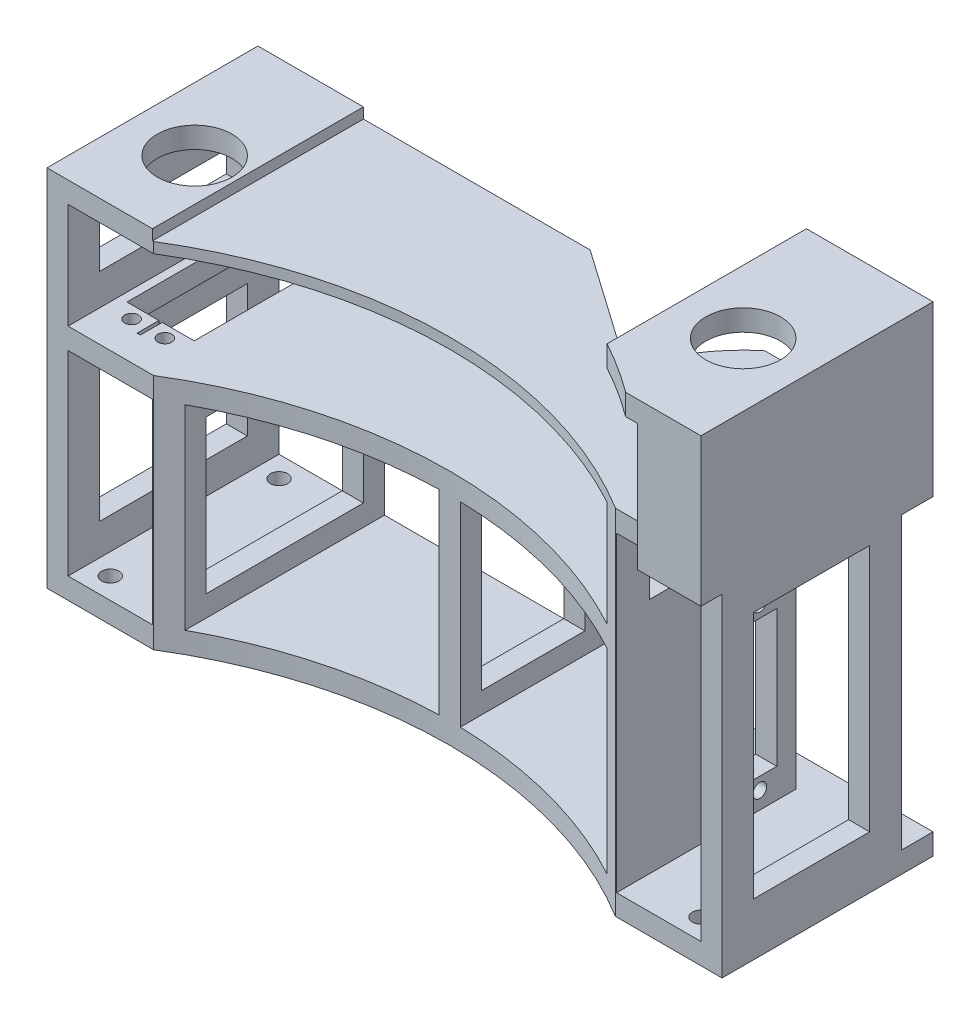
SolidWorks part; units mm, degrees
ref_plane "Front Plane" through (0, 0, 0) normal (0, 0, 1) x (1, 0, 0)
ref_plane "Top Plane" through (0, 0, 0) normal (0, 1, 0) x (1, 0, 0)
ref_plane "Right Plane" through (0, 0, 0) normal (1, 0, 0) x (0, 0, -1)
sketch "Sketch1" plane through (0, 0, 0) normal (0, 0, 1) x (1, 0, 0)
  line L0 (-101.6, 106.425) -> (101.6, 106.425)
  line L1 (-101.6, 0) -> (101.6, 0)
  line L2 (-101.6, 0) -> (-101.6, 106.425)
  line L4 (101.6, 0) -> (101.6, 106.425)
  point P5 (0, 0)
  dimension "D1" = 203.2
  dimension "D2" = 106.425
extrude "Boss-Extrude1" add sketch "Sketch1" along normal mid plane 63.5 contours L1 L4 L0 L2 | L0 region at (0, 53.2125, 0)
sketch "Sketch4" plane through (0, 0, -31.75) normal (0, 0, -1) x (-1, 0, 0)
  line L0 (-101.6, 0) -> (-101.6, 106.425) construction
  line L1 (101.6, 0) -> (101.6, 106.425) construction
  line L2 (-95.25, 103.25) -> (95.25, 103.25)
  line L3 (-95.25, 103.25) -> (-95.25, 71.5)
  line L4 (-95.25, 71.5) -> (95.25, 71.5)
  line L5 (95.25, 103.25) -> (95.25, 71.5)
  line L11 (-95.25, 65.15) -> (95.25, 65.15)
  line L12 (-95.25, 65.15) -> (-95.25, 6.35)
  line L13 (-95.25, 6.35) -> (95.25, 6.35)
  line L14 (95.25, 65.15) -> (95.25, 6.35)
  line L15 (101.6, 0) -> (-101.6, 0) construction
  dimension "D4" = 6.35
  dimension "D1" = 6.35
  dimension "D2" = 71.5
  dimension "D3" = 6.35
  dimension "D5" = 6.35
  dimension "D6" = 31.75
extrude "Cut-Extrude2" cut sketch "Sketch4" against normal through all
sketch "Sketch8" plane through (0, 0, 0) normal (0, 0, 1) x (1, 0, 0)
  line L0 (-95.25, 65.15) -> (95.25, 65.15) construction
  line L1 (-69.85, 65.15) -> (-63.5, 65.15)
  line L2 (-69.85, 65.15) -> (-69.85, 6.35)
  line L3 (-69.85, 6.35) -> (-63.5, 6.35)
  line L4 (-63.5, 65.15) -> (-63.5, 6.35)
  line L5 (95.25, 6.35) -> (-95.25, 6.35) construction
  line L6 (-95.25, 103.25) -> (95.25, 103.25) construction
  line L7 (63.5, 103.25) -> (69.85, 103.25)
  line L8 (63.5, 103.25) -> (63.5, 6.35)
  line L9 (63.5, 6.35) -> (69.85, 6.35)
  line L10 (69.85, 103.25) -> (69.85, 6.35)
  line L11 (95.25, 65.15) -> (95.25, 6.35) construction
  line L12 (-95.25, 6.35) -> (-95.25, 65.15) construction
  line L13 (-101.6, 0) -> (101.6, 0) construction
  line L14 (-3.175, 65.15) -> (3.175, 65.15)
  line L15 (-3.175, 65.15) -> (-3.175, 6.35)
  line L16 (-3.175, 6.35) -> (3.175, 6.35)
  line L17 (3.175, 65.15) -> (3.175, 6.35)
  point P24 (0, 0)
  point P25 (0, 6.35)
  dimension "D1" = 6.35
  dimension "D2" = 6.35
  dimension "D3" = 25.4
  dimension "D4" = 25.4
  dimension "D5" = 6.35
extrude "Boss-Extrude2" add sketch "Sketch8" along normal up to surface (31.75 mm away) from surface up to face at (0, 87.375, 31.75) starting at face at (0, 87.375, -31.75)
sketch "Sketch15" plane through (0, 103.25, 0) normal (0, -1, 0) x (1, 0, 0)
  line L4 (69.85, 31.75) -> (69.85, -31.75)
  line L5 (69.85, -31.75) -> (95.25, -31.75)
  line L6 (95.25, -31.75) -> (95.25, 31.75)
  line L7 (95.25, 31.75) -> (69.85, 31.75)
  line L8 (69.85, 31.75) -> (69.85, -31.75)
  line L9 (69.85, -31.75) -> (95.25, -31.75)
  line L10 (95.25, -31.75) -> (95.25, 31.75)
  line L11 (95.25, 31.75) -> (69.85, 31.75)
  dimension "D1" = 0
extrude "Boss-Extrude4" add sketch "Sketch15" along normal blind 3.175
sketch "Sketch2" plane through (0, 71.5, 0) normal (0, 1, 0) x (1, 0, 0)
  line L0 (-92.677, 24.55) -> (-72.423, -16.604) construction
  line L29 (-92.677, 24.55) -> (-83.05, 24.55)
  line L30 (-92.677, 24.55) -> (-92.677, -16.604)
  line L31 (-92.677, -16.604) -> (-83.05, -16.604)
  line L34 (-72.423, 24.55) -> (-72.423, -16.604)
  line L58 (69.85, 31.75) -> (69.85, -31.75)
  line L59 (69.85, -31.75) -> (95.25, -31.75)
  line L60 (95.25, -31.75) -> (95.25, 31.75)
  line L61 (95.25, 31.75) -> (69.85, 31.75)
  line L62 (69.85, 31.75) -> (69.85, -31.75)
  line L63 (69.85, -31.75) -> (95.25, -31.75)
  line L64 (95.25, -31.75) -> (95.25, 31.75)
  line L65 (95.25, 31.75) -> (69.85, 31.75)
  line L78 (-72.423, 24.55) -> (-92.677, -16.604) construction
  line L79 (-87.55, 28.273) -> (-77.55, -20.327) construction
  line L80 (-87.55, -20.327) -> (-77.55, 28.273) construction
  line L81 (-82.05, -16.604) -> (-72.423, -16.604)
  line L82 (-82.05, -16.604) -> (-82.05, -23.208)
  line L83 (-82.05, -23.208) -> (-83.05, -23.208)
  line L84 (-83.05, -16.604) -> (-83.05, -23.208)
  line L85 (-82.55, 3.973) -> (-13.3966, 3.973) construction
  line L86 (-82.05, 31.154) -> (-83.05, 31.154)
  line L87 (-82.05, 24.55) -> (-82.05, 31.154)
  line L88 (-83.05, 24.55) -> (-83.05, 31.154)
  line L89 (-82.05, 24.55) -> (-72.423, 24.55)
  line L90 (-101.6, -31.75) -> (101.6, -31.75) construction
  line L91 (-101.6, -31.75) -> (-101.6, 31.75) construction
  circle A12 centre (-87.55, -20.327) radius 2.1
  circle A13 centre (-77.55, -20.327) radius 2.1
  circle A14 centre (-87.55, 28.273) radius 2.1
  circle A15 centre (-77.55, 28.273) radius 2.1
  point P8 (-82.55, -23.208)
  point P17 (-82.55, 3.973)
  point P18 (-82.55, 3.973)
  point P27 (-82.55, -6.35)
  dimension "D3" = 48.6
  dimension "D4" = 4.2
  dimension "D2" = 10
  dimension "D5" = 41.154
  dimension "D6" = 20.254
  dimension "D7" = 1
  dimension "D8" = 6.604
  dimension "D9" = 30.9
  dimension "D10" = 25.4
  dimension "D11" = 0
  dimension "D12" = 19.05
extrude "Cut-Extrude3" cut sketch "Sketch2" against normal up to next
sketch "Sketch9" plane through (0, 106.425, 0) normal (0, 1, 0) x (1, 0, 0)
  line L0 (72.423, 24.55) -> (92.677, -16.604) construction
  line L1 (72.423, 24.55) -> (82.05, 24.55)
  line L2 (72.423, 24.55) -> (72.423, -16.604)
  line L3 (72.423, -16.604) -> (82.05, -16.604)
  line L4 (92.677, 24.55) -> (92.677, -16.604)
  line L5 (92.677, 24.55) -> (72.423, -16.604) construction
  line L6 (77.55, 28.273) -> (87.55, -20.327) construction
  line L7 (77.55, -20.327) -> (87.55, 28.273) construction
  line L8 (83.05, -16.604) -> (92.677, -16.604)
  line L9 (83.05, -16.604) -> (83.05, -23.208)
  line L10 (83.05, -23.208) -> (82.05, -23.208)
  line L11 (82.05, -16.604) -> (82.05, -23.208)
  line L12 (82.55, 3.973) -> (164.4034, 3.973) construction
  line L13 (83.05, 31.154) -> (82.05, 31.154)
  line L14 (83.05, 24.55) -> (83.05, 31.154)
  line L15 (82.05, 24.55) -> (82.05, 31.154)
  line L16 (83.05, 24.55) -> (92.677, 24.55)
  line L17 (101.6, -31.75) -> (101.6, 31.75) construction
  line L19 (-101.6, -31.75) -> (101.6, -31.75) construction
  circle A0 centre (77.55, -20.327) radius 2.1
  circle A1 centre (87.55, -20.327) radius 2.1
  circle A2 centre (77.55, 28.273) radius 2.1
  circle A3 centre (87.55, 28.273) radius 2.1
  point P8 (82.55, -23.208)
  point P17 (82.55, 3.973)
  point P18 (82.55, 3.973)
  point P27 (82.55, -6.35)
  dimension "D3" = 4.2
  dimension "D1" = 10
  dimension "D2" = 48.6
  dimension "D4" = 41.154
  dimension "D5" = 20.254
  dimension "D6" = 1
  dimension "D7" = 6.604
  dimension "D8" = 30.9
  dimension "D9" = 19.05
  dimension "D10" = 25.4
extrude "Cut-Extrude4" cut sketch "Sketch9" against normal up to next
sketch "Sketch12" plane through (0, 0, 0) normal (0, 1, 0) x (1, 0, 0)
  line L0 (-63.5, -31.75) -> (-63.5, 31.75) construction
  line L1 (-69.85, -31.75) -> (-95.25, -31.75) construction
  line L2 (-95.25, -31.75) -> (-95.25, 31.75) construction
  line L3 (-101.6, 31.75) -> (101.6, 31.75) construction
  circle A0 centre (-88.9, 25.4) radius 2.6
  circle A1 centre (-88.9, -25.4) radius 2.6
  circle A2 centre (-31.75, 25.4) radius 2.6
  dimension "D1" = 5.2
  dimension "D2" = 6.35
  dimension "D3" = 6.35
  dimension "D4" = 6.35
  dimension "D5" = 31.75
extrude "Cut-Extrude7" cut sketch "Sketch12" along normal up to surface (6.35 mm away) and the other way through all up to face at (-33.3375, 6.35, 0)
mirror "Mirror1" about plane through (0, 0, 0) normal (1, 0, 0) of "Cut-Extrude7"
sketch "Sketch16" plane through (0, 106.425, 0) normal (0, 1, 0) x (1, 0, 0)
  line L2 (-69.85, 31.75) -> (-101.6, 31.75)
  line L3 (-101.6, 31.75) -> (-101.6, -31.75)
  line L12 (-101.6, -31.75) -> (-69.85, -31.75)
  line L13 (-69.85, 31.75) -> (-69.85, -31.75)
  dimension "D1" = 31.75
extrude "Boss-Extrude5" add sketch "Sketch16" along normal blind 3.175
sketch "Sketch17" plane through (0, 109.6, 0) normal (0, 1, 0) x (1, 0, 0)
  line L0 (-101.6, -31.75) -> (-69.85, -31.75) construction
  line L1 (-101.6, 31.75) -> (-101.6, -31.75) construction
  circle A0 centre (-82.55, -6.35) radius 11.2395
  dimension "D3" = 22.479
  dimension "D1" = 25.4
  dimension "D2" = 19.05
extrude "Cut-Extrude8" cut sketch "Sketch17" against normal up to next
sketch "Sketch18" plane through (0, 106.425, 0) normal (0, 1, 0) x (1, 0, 0)
  line L5 (101.6, -31.75) -> (101.6, 31.75) construction
  line L6 (-69.85, -31.75) -> (101.6, -31.75) construction
  line L14 (101.6, -31.75) -> (101.6, 31.75)
  line L15 (101.6, 31.75) -> (95.25, 31.75)
  line L16 (95.25, -31.75) -> (95.25, 31.75)
  line L22 (95.25, -31.75) -> (82.55, -31.75)
  line L23 (101.6, -31.75) -> (101.6, -38.1)
  line L24 (101.6, -38.1) -> (82.55, -38.1)
  line L25 (82.55, -31.75) -> (82.55, -38.1)
  dimension "D4" = 6.35
  dimension "D5" = 19.05
extrude "Boss-Extrude6" add sketch "Sketch18" along normal blind 38.1 from surface starting at face at (87.55, 100.075, 18.227)
sketch "Sketch20" plane through (0, 138.175, 0) normal (0, 1, 0) x (1, 0, 0)
  line L1 (63.5, 31.75) -> (101.6, 31.75)
  line L2 (63.5, 31.75) -> (63.5, -38.1)
  line L3 (63.5, -38.1) -> (101.6, -38.1)
  line L4 (101.6, 31.75) -> (101.6, -38.1)
  line L6 (-69.85, -31.75) -> (82.55, -31.75) construction
  circle A0 centre (82.55, -6.35) radius 11.2395
  dimension "D2" = 19.05
  dimension "D1" = 22.479
  dimension "D4" = 38.1
  dimension "D3" = 25.4
extrude "Boss-Extrude7" add sketch "Sketch20" along normal blind 6.35
sketch "Sketch10" plane through (0, 106.425, 0) normal (0, 1, 0) x (1, 0, 0)
  circle A3 centre (0, -144.78) radius 131.1117 construction
  circle A4 centre (0, -144.78) radius 131.1117 construction
  circle A5 centre (0, -144.78) radius 132.6992
  dimension "D1" = 1.5875
extrude "Cut-Extrude5" cut sketch "Sketch10" against normal through all both and the other way through all
sketch "Sketch21" plane through (0, 106.425, 0) normal (0, 1, 0) x (1, 0, 0)
  line L5 (34.6759, 6.35) -> (-1.5991, 31.75)
  line L6 (-69.85, 31.75) -> (95.25, 31.75) construction
  line L7 (-1.5991, 31.75) -> (50.9018, 31.75)
  arc A1 (34.6759, 6.35) -> (50.9018, 31.75) centre (82.55, -6.35) cw
  dimension "D2" = 49.53
  dimension "D1" = 35
  dimension "D3" = 25.4
extrude "Cut-Extrude10" cut sketch "Sketch21" against normal up to surface (3.175 mm away) up to face at (-82.55, 103.25, 17.5895)
sketch "Sketch32" plane through (0, 6.35, 0) normal (0, 1, 0) x (1, 0, 0)
  line L4 (-88.9, -25.4) -> (-76.2, -25.4)
  line L5 (-88.9, -25.4) -> (-76.2, -25.4)
  line L6 (76.2, -25.4) -> (88.9, -25.4)
  line L7 (76.2, -25.4) -> (88.9, -25.4)
  line L8 (76.2, 25.4) -> (76.2, -25.4)
  line L9 (88.9, -25.4) -> (88.9, 25.4)
  line L10 (88.9, 25.4) -> (76.2, 25.4)
  line L11 (76.2, 25.4) -> (76.2, -25.4)
  line L12 (88.9, -16.45) -> (88.9, 16.45)
  line L13 (79.95, 25.4) -> (76.2, 25.4)
  line L32 (-57.15, 25.4) -> (-57.15, -18.0181)
  line L33 (-9.525, -6.0574) -> (-9.525, 25.4)
  line L40 (-76.2, -25.4) -> (-76.2, 25.4)
  line L41 (-76.2, 25.4) -> (-88.9, 25.4)
  line L42 (-88.9, 25.4) -> (-88.9, -25.4)
  line L43 (-76.2, -25.4) -> (-76.2, 25.4)
  line L44 (-76.2, 25.4) -> (-79.95, 25.4)
  line L45 (-88.9, 16.45) -> (-88.9, -16.45)
  line L48 (-9.525, 25.4) -> (-57.15, 25.4)
  line L49 (-57.15, 25.4) -> (-57.15, -18.0181)
  line L50 (-9.525, -6.0574) -> (-9.525, 25.4)
  line L67 (-9.525, 25.4) -> (-22.8, 25.4)
  line L68 (-40.7, 25.4) -> (-57.15, 25.4)
  line L69 (22.8, 25.4) -> (9.525, 25.4)
  line L71 (9.525, 25.4) -> (9.525, -6.0574)
  line L72 (57.15, -18.0181) -> (57.15, 25.4)
  line L73 (57.15, 25.4) -> (9.525, 25.4)
  line L74 (9.525, 25.4) -> (9.525, -6.0574)
  line L75 (57.15, -18.0181) -> (57.15, 25.4)
  line L76 (57.15, 25.4) -> (40.7, 25.4)
  circle A2 centre (88.9, 25.4) radius 8.95
  arc A3 (79.95, 25.4) -> (88.9, 16.45) centre (88.9, 25.4) ccw
  circle A9 centre (88.9, -25.4) radius 8.95
  arc A10 (88.9, -16.45) -> (81.9575, -19.7516) centre (88.9, -25.4) ccw
  circle A13 centre (-31.75, 25.4) radius 8.95
  arc A26 (-40.7, 25.4) -> (-22.8, 25.4) centre (-31.75, 25.4) ccw
  circle A27 centre (-88.9, 25.4) radius 8.95
  arc A28 (-88.9, 16.45) -> (-79.95, 25.4) centre (-88.9, 25.4) ccw
  circle A30 centre (-88.9, -25.4) radius 8.95
  arc A31 (-80.2186, -23.2237) -> (-88.9, -16.45) centre (-88.9, -25.4) ccw
  circle A33 centre (31.75, 25.4) radius 8.95
  arc A35 (22.8, 25.4) -> (40.7, 25.4) centre (31.75, 25.4) ccw
  arc A38 (-9.525, -6.0574) -> (-57.15, -18.0181) centre (0, -144.78) ccw
  arc A39 (-9.525, -6.0574) -> (-57.15, -18.0181) centre (0, -144.78) ccw
  arc A42 (57.15, -18.0181) -> (9.525, -6.0574) centre (0, -144.78) ccw
  arc A43 (57.15, -18.0181) -> (9.525, -6.0574) centre (0, -144.78) ccw
  dimension "D1" = 6.35
  dimension "D2" = 6.35
  dimension "D3" = 6.35
  dimension "D4" = 6.35
  dimension "D5" = 6.35
  dimension "D6" = 6.35
  dimension "D7" = 6.35
  dimension "D8" = 6.35
  dimension "D9" = 6.35
  dimension "D10" = 6.35
extrude "Cut-Extrude19" cut sketch "Sketch32" against normal up to next rebuild error yes
sketch "Sketch23" plane through (0, 0, -31.75) normal (0, 0, -1) x (-1, 0, 0)
  line L1 (-101.6, 6.35) -> (-57.15, 6.35)
  line L2 (-101.6, 6.35) -> (-101.6, 93.725)
  line L3 (-101.6, 93.725) -> (-57.15, 93.725)
  line L4 (-57.15, 6.35) -> (-57.15, 93.725)
  line L7 (-63.5, 71.5) -> (95.25, 71.5) construction
  line L9 (-63.5, 65.15) -> (-63.5, 6.35) construction
  line L10 (-101.6, 0) -> (-101.6, 144.525) construction
  line L11 (-63.5, 6.35) -> (-3.175, 6.35) construction
  dimension "D1" = 6.35
  dimension "D2" = 22.225
extrude "Cut-Extrude11" cut sketch "Sketch23" against normal blind 9.525
sketch "Sketch24" plane through (63.5, 0, 0) normal (-1, 0, 0) x (0, 0, 1)
  line L0 (-16.477, 56.354) -> (3.777, 15.2) construction
  line L1 (-16.477, 56.354) -> (-6.85, 56.354)
  line L2 (-16.477, 56.354) -> (-16.477, 15.2)
  line L3 (-16.477, 15.2) -> (-6.85, 15.2)
  line L4 (3.777, 56.354) -> (3.777, 15.2)
  line L5 (3.777, 56.354) -> (-16.477, 15.2) construction
  line L6 (-11.35, 60.077) -> (-1.35, 11.477) construction
  line L7 (-11.35, 11.477) -> (-1.35, 60.077) construction
  line L8 (-5.85, 15.2) -> (3.777, 15.2)
  line L9 (-5.85, 15.2) -> (-5.85, 8.596)
  line L10 (-5.85, 8.596) -> (-6.85, 8.596)
  line L11 (-6.85, 15.2) -> (-6.85, 8.596)
  line L12 (-6.35, 35.777) -> (65.4757, 35.777) construction
  line L13 (-5.85, 62.958) -> (-6.85, 62.958)
  line L14 (-5.85, 56.354) -> (-5.85, 62.958)
  line L15 (-6.85, 56.354) -> (-6.85, 62.958)
  line L16 (-5.85, 56.354) -> (3.777, 56.354)
  line L17 (-22.225, 65.15) -> (-22.225, 6.35) construction
  line L18 (28.2603, 65.15) -> (-22.225, 65.15) construction
  circle A0 centre (-11.35, 11.477) radius 2.1
  circle A1 centre (-1.35, 11.477) radius 2.1
  circle A2 centre (-11.35, 60.077) radius 2.1
  circle A3 centre (-1.35, 60.077) radius 2.1
  point P8 (-6.35, 8.596)
  point P17 (-6.35, 35.777)
  point P18 (-6.35, 35.777)
  point P27 (-6.35, 46.1)
  dimension "D3" = 4.2
  dimension "D1" = 10
  dimension "D2" = 48.6
  dimension "D4" = 41.154
  dimension "D5" = 20.254
  dimension "D6" = 1
  dimension "D7" = 6.604
  dimension "D8" = 30.9
  dimension "D9" = 15.875
  dimension "D10" = 19.05
extrude "Cut-Extrude12" cut sketch "Sketch24" against normal up to next
sketch "Sketch26" plane through (95.25, 0, 0) normal (-1, 0, 0) x (0, 0, 1)
  line L12 (-12.7, 90.55) -> (-12.7, 15.875)
  line L13 (-12.7, 15.875) -> (22.225, 15.875)
  line L14 (22.225, 15.875) -> (22.225, 90.55)
  line L15 (22.225, 90.55) -> (-12.7, 90.55)
  line L16 (-12.7, 90.55) -> (-12.7, 15.875)
  line L17 (-12.7, 15.875) -> (22.225, 15.875)
  line L18 (22.225, 15.875) -> (22.225, 90.55)
  line L19 (22.225, 90.55) -> (-12.7, 90.55)
  dimension "D1" = 9.525
extrude "Cut-Extrude13" cut sketch "Sketch26" against normal up to next
sketch "Sketch27" plane through (63.5, 0, 0) normal (-1, 0, 0) x (0, 0, 1)
  line L6 (21.9103, 77.85) -> (21.9103, 96.9)
  line L8 (21.9103, 77.85) -> (21.9103, 96.9)
  line L12 (-15.875, 96.9) -> (-15.875, 77.85)
  line L13 (-15.875, 77.85) -> (21.9103, 77.85)
  line L15 (21.9103, 96.9) -> (-15.875, 96.9)
  line L16 (-15.875, 96.9) -> (-15.875, 77.85)
  line L17 (-15.875, 77.85) -> (21.9103, 77.85)
  line L19 (21.9103, 96.9) -> (-15.875, 96.9)
  dimension "D1" = 6.35
extrude "Cut-Extrude14" cut sketch "Sketch27" against normal up to next
sketch "Sketch28" plane through (3.175, 0, 0) normal (1, 0, 0) x (0, 0, -1)
  line L8 (25.4, 58.8) -> (-5.7687, 58.8)
  line L9 (-5.7687, 58.8) -> (-5.7687, 12.7)
  line L10 (-5.7687, 12.7) -> (25.4, 12.7)
  line L11 (25.4, 12.7) -> (25.4, 58.8)
  line L12 (25.4, 58.8) -> (-5.7687, 58.8)
  line L13 (-5.7687, 58.8) -> (-5.7687, 12.7)
  line L14 (-5.7687, 12.7) -> (25.4, 12.7)
  line L15 (25.4, 12.7) -> (25.4, 58.8)
  dimension "D1" = 6.35
extrude "Cut-Extrude15" cut sketch "Sketch28" against normal up to next
sketch "Sketch29" plane through (-63.5, 0, 0) normal (1, 0, 0) x (0, 0, -1)
  line L8 (25.4, 58.8) -> (-21.9103, 58.8)
  line L9 (-21.9103, 58.8) -> (-21.9103, 12.7)
  line L10 (-21.9103, 12.7) -> (25.4, 12.7)
  line L11 (25.4, 12.7) -> (25.4, 58.8)
  line L12 (25.4, 58.8) -> (-21.9103, 58.8)
  line L13 (-21.9103, 58.8) -> (-21.9103, 12.7)
  line L14 (-21.9103, 12.7) -> (25.4, 12.7)
  line L15 (25.4, 12.7) -> (25.4, 58.8)
  dimension "D1" = 6.35
extrude "Cut-Extrude16" cut sketch "Sketch29" against normal up to next
sketch "Sketch30" plane through (-95.25, 0, 0) normal (1, 0, 0) x (0, 0, -1)
  line L8 (22.225, 15.875) -> (22.225, 55.625)
  line L9 (22.225, 55.625) -> (-22.225, 55.625)
  line L10 (-22.225, 55.625) -> (-22.225, 15.875)
  line L11 (-22.225, 15.875) -> (22.225, 15.875)
  line L12 (22.225, 15.875) -> (22.225, 55.625)
  line L13 (22.225, 55.625) -> (-22.225, 55.625)
  line L14 (-22.225, 55.625) -> (-22.225, 15.875)
  line L15 (-22.225, 15.875) -> (22.225, 15.875)
  dimension "D1" = 9.525
extrude "Cut-Extrude17" cut sketch "Sketch30" against normal up to next
sketch "Sketch31" plane through (-95.25, 0, 0) normal (1, 0, 0) x (0, 0, -1)
  line L4 (22.225, 81.025) -> (22.225, 93.725)
  line L6 (22.225, 81.025) -> (22.225, 93.725)
  line L9 (22.225, 93.725) -> (-22.225, 93.725)
  line L10 (-22.225, 93.725) -> (-22.225, 81.025)
  line L11 (-22.225, 81.025) -> (22.225, 81.025)
  line L13 (22.225, 93.725) -> (-22.225, 93.725)
  line L14 (-22.225, 93.725) -> (-22.225, 81.025)
  line L15 (-22.225, 81.025) -> (22.225, 81.025)
  dimension "D1" = 9.525
extrude "Cut-Extrude18" cut sketch "Sketch31" against normal up to next
fillet "Fillet1" radius 9.525 1 edges at (34.6759, 104.8375, -6.35)
equation "\"tightTol\"= 0.005in"
equation "\"normTol\"= 0.01in"
equation "\"looseTol\"= 0.02in"
equation "\"D1@Sketch12\"=5.2mm"
equation "\"D2@Sketch1\"=8mm+0.5+3.25+0.125"
equation "\"D2@Sketch4\"=8mm+0.25+2.25"
equation "\"D3@Sketch17\" = 7 / 8 + \"normTol\""
equation "\"D1@Sketch20\"=7/8+\"normTol\""
